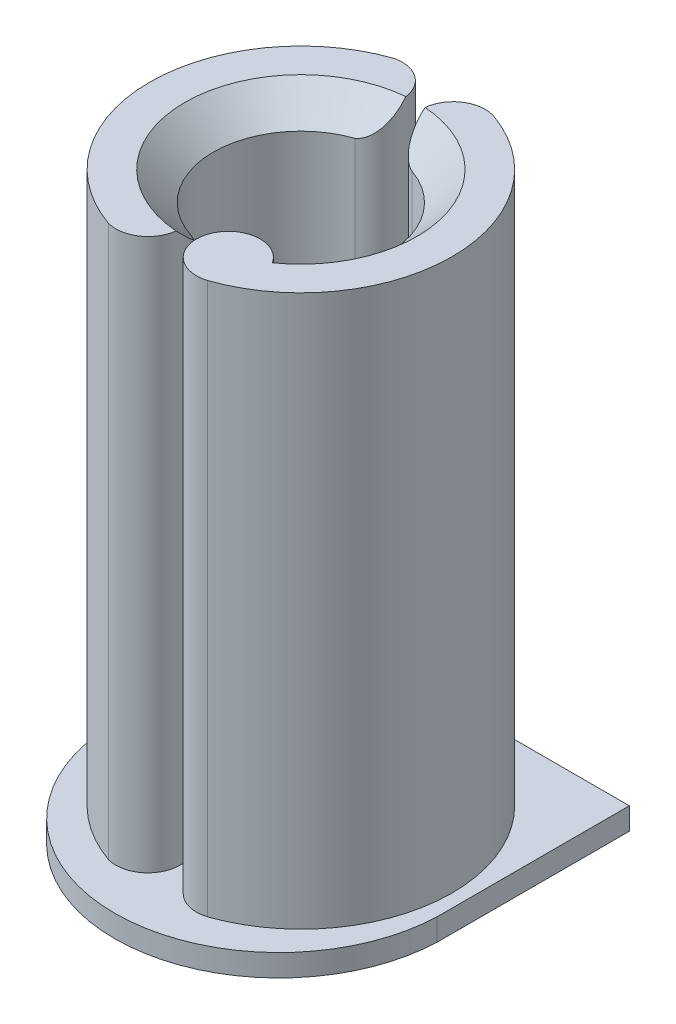
SolidWorks part; units mm, degrees
ref_plane "Plano frontal" through (0, 0, 0) normal (0, 0, 1) x (1, 0, 0)
ref_plane "Plano superior" through (0, 0, 0) normal (0, 1, 0) x (1, 0, 0)
ref_plane "Plano direito" through (0, 0, 0) normal (1, 0, 0) x (0, 0, -1)
sketch "Esboço1" plane through (0, 0, 0) normal (0, 1, 0) x (1, 0, 0)
  line L2 (-0.745, -0.1273) -> (-0.745, 0.745)
  line L3 (-0.745, 0.745) -> (0.745, 0.745)
  line L4 (0.745, -0.1273) -> (0.745, 0.745)
  arc A1 (0.745, -0.1273) -> (-0.745, -0.1273) centre (0, -0.099) cw
  dimension "D2" = 1.49
extrude "Ressalto-extrusão2" add sketch "Esboço1" along normal blind 0.1
sketch "Esboço2" plane through (0, 0.1, 0) normal (0, 1, 0) x (1, 0, 0)
  arc A0 (-0.1301, 0.3747) -> (-0.1202, -0.378) centre (0, 0) ccw
  arc A1 (0.225, -0.6478) -> (0.2305, 0.6459) centre (0, 0) ccw
  arc A6 (-0.225, 0.6478) -> (-0.225, -0.6478) centre (0, 0) ccw
  arc A7 (0.1368, -0.3723) -> (0.1301, 0.3747) centre (0, 0) ccw
  arc A9 (-0.225, 0.6478) -> (-0.1301, 0.3747) centre (-0.1924, 0.5061) cw
  arc A10 (0.2305, 0.6459) -> (0.1301, 0.3747) centre (0.1819, 0.5097) ccw
  arc A11 (-0.225, -0.6478) -> (-0.1202, -0.378) centre (-0.186, -0.5077) ccw
  arc A12 (0.225, -0.6478) -> (0.1368, -0.3723) centre (0.1809, -0.5101) cw
extrude "Ressalto-extrusão4" add sketch "Esboço2" along normal blind 2.5
chamfer "Chanfro4" distance 0.13 angle 45 1 edges at (-0.3966, 2.6, 0.0052)
chamfer "Chanfro6" distance 0.13 angle 45 1 edges at (0.3966, 2.6, -0.0035)
